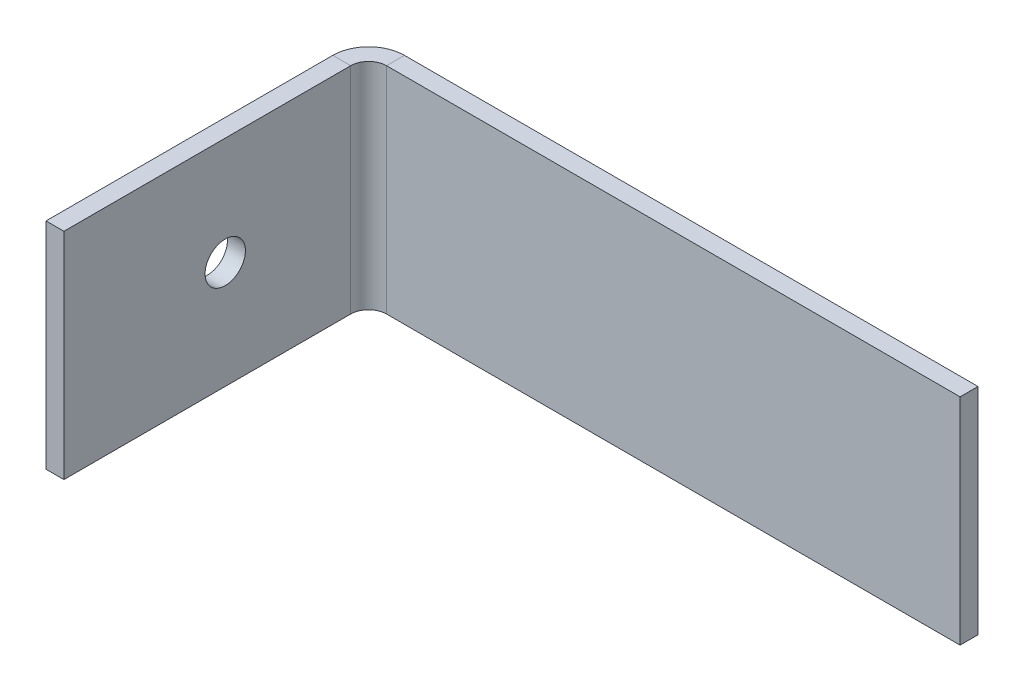
SolidWorks part; units mm, degrees
note: The reader was unsure of these and kept them because the rebuilt part matched: flange length of "Edge-Flange4".
ref_plane "Front Plane" through (0, 0, 0) normal (0, 0, 1) x (1, 0, 0)
ref_plane "Top Plane" through (0, 0, 0) normal (0, 1, 0) x (1, 0, 0)
ref_plane "Right Plane" through (0, 0, 0) normal (1, 0, 0) x (0, 0, -1)
sketch "Sketch1" plane through (0, 0, 0) normal (0, 0, 1) x (1, 0, 0)
  line L0 (0, 226.9984) -> (0, -403.8278) construction
  line L1 (-574.8759, 0) -> (658.4709, 0) construction
  line L3 (-307.975, -2286) -> (-330.2, -2286)
  line L4 (-307.975, -2286) -> (-307.975, 2286)
  line L5 (-307.975, 2286) -> (-330.2, 2286)
  line L6 (-330.2, -2286) -> (-330.2, 2286)
  line L7 (-307.975, -2286) -> (-330.2, 2286) construction
  line L8 (-307.975, 2286) -> (-330.2, -2286) construction
  point P5 (-319.0875, 0)
  dimension "D1" = 22.225
  dimension "D2" = 4572
  dimension "D3" = 330.2
sketch "Sketch19" plane through (0, 0, 0) normal (0, 0, 1) x (1, 0, 0)
  line L0 (0, 94.8905) -> (0, -94.5535) construction
  line L1 (-231.2496, 0) -> (245.8658, 0) construction
  line L3 (107.95, -38.1) -> (-107.95, -38.1)
  line L4 (107.95, -38.1) -> (107.95, 38.1)
  line L5 (107.95, 38.1) -> (-107.95, 38.1)
  line L6 (-107.95, -38.1) -> (-107.95, 38.1)
  line L7 (107.95, -38.1) -> (-107.95, 38.1) construction
  line L8 (107.95, 38.1) -> (-107.95, -38.1) construction
  point P6 (0, 0)
  dimension "D1" = 215.9
  dimension "D2" = 76.2
base flange "Base-Flange2" sketch "Sketch19" thickness 6.35 reverse thickness direction no parameters "D1"=25.4
edge flange "Edge-Flange4" sketch "Sketch26" flange angle 90 flange length 114.3 flange position material inside bend radius 6.35 thickness 6.35 relief rectangular parameters "D6"=0
sketch "Sketch26" plane through (-107.95, 0, 0) normal (-1, 0, 0) x (0, -1, 0)
  line L0 (-38.1, 0) -> (38.1, 0) construction
  line L1 (-38.1, 0) -> (38.1, 0)
  line L2 (-38.1, 0) -> (-38.1, 107.95)
  line L3 (-38.1, 107.95) -> (38.1, 107.95)
  line L4 (38.1, 107.95) -> (38.1, 0)
bend "EdgeBend4" bend radius 6.35 bend angle 90 parameters "D5"=1
sketch "Sketch27" plane through (-101.6, 0, 0) normal (1, 0, 0) x (0, 0, -1)
  line L0 (-166.6945, 0) -> (101.3288, 0) construction
  line L1 (-107.95, -38.1) -> (-107.95, 38.1) construction
  circle A0 centre (-50.8, 0) radius 7.1438
  dimension "D1" = 14.2875
  dimension "D2" = 57.15
extrude "Cut-Extrude1" cut sketch "Sketch27" against normal up to next normal cut yes
sketch "Bend-Lines3" [suppressed] plane through (0, 0, 0) normal (0, 1, 0) x (1, 0, 0)
sketch "Bounding-Box3" [suppressed] plane through (0, 0, 0) normal (0, 1, 0) x (1, 0, 0)
sheet metal parameters "Sheet-Metal5" thickness 6.35 parameters "D1"=25.4
flat pattern "Flat-Pattern5" [suppressed]
sketch "Bend-Lines4" plane through (0, 0, 0) normal (0, 1, 0) x (1, 0, 0)
sketch3d "Bounding-Box4" [suppressed]
  line L0 (107.95, -38.1, 0) -> (-107.95, -38.1, 0) construction
  line L1 (107.95, 38.1, 0) -> (-107.95, 38.1, 0) construction
  line L2 (107.95, -38.1, 0) -> (107.95, 38.1, 0) construction
  line L3 (-107.95, -38.1, 0) -> (-107.95, 38.1, 0) construction
sheet metal parameters "Sheet-Metal6" thickness 6.35 parameters "D1"=25.4
flat pattern "Flat-Pattern5"
sketch "Bend-Lines4" plane through (0, 0, 0) normal (0, 0, 1) x (1, 0, 0)
  line L0 (-102.7309, 38.1) -> (-102.7309, -38.1) construction
  line L1 (-102.7309, 38.1) -> (-102.7309, -38.1) construction
sketch3d "Bounding-Box4" [suppressed]
  line L0 (-211.8118, -38.1, 0) -> (107.95, -38.1, 0) construction
  line L1 (-211.8118, 38.1, 0) -> (107.95, 38.1, 0) construction
  line L2 (-211.8118, -38.1, 0) -> (-211.8118, 38.1, 0) construction
  line L3 (107.95, -38.1, 0) -> (107.95, 38.1, 0) construction
bend of the flat pattern "Flatten-<EdgeBend4>1"
sheet metal parameters "Sheet-Metal7" thickness 6.35 parameters "D1"=25.4
flat pattern "Flat-Pattern5"
sketch "Bend-Lines4" plane through (0, 0, 0) normal (0, 0, 1) x (1, 0, 0)
  line L0 (-102.7309, 38.1) -> (-102.7309, -38.1) construction
  line L1 (-102.7309, 38.1) -> (-102.7309, -38.1) construction
sketch3d "Bounding-Box4" [suppressed]
  line L0 (-211.8118, -38.1, 0) -> (107.95, -38.1, 0) construction
  line L1 (-211.8118, 38.1, 0) -> (107.95, 38.1, 0) construction
  line L2 (-211.8118, -38.1, 0) -> (-211.8118, 38.1, 0) construction
  line L3 (107.95, -38.1, 0) -> (107.95, 38.1, 0) construction
bend of the flat pattern "Flatten-<EdgeBend4>1"
